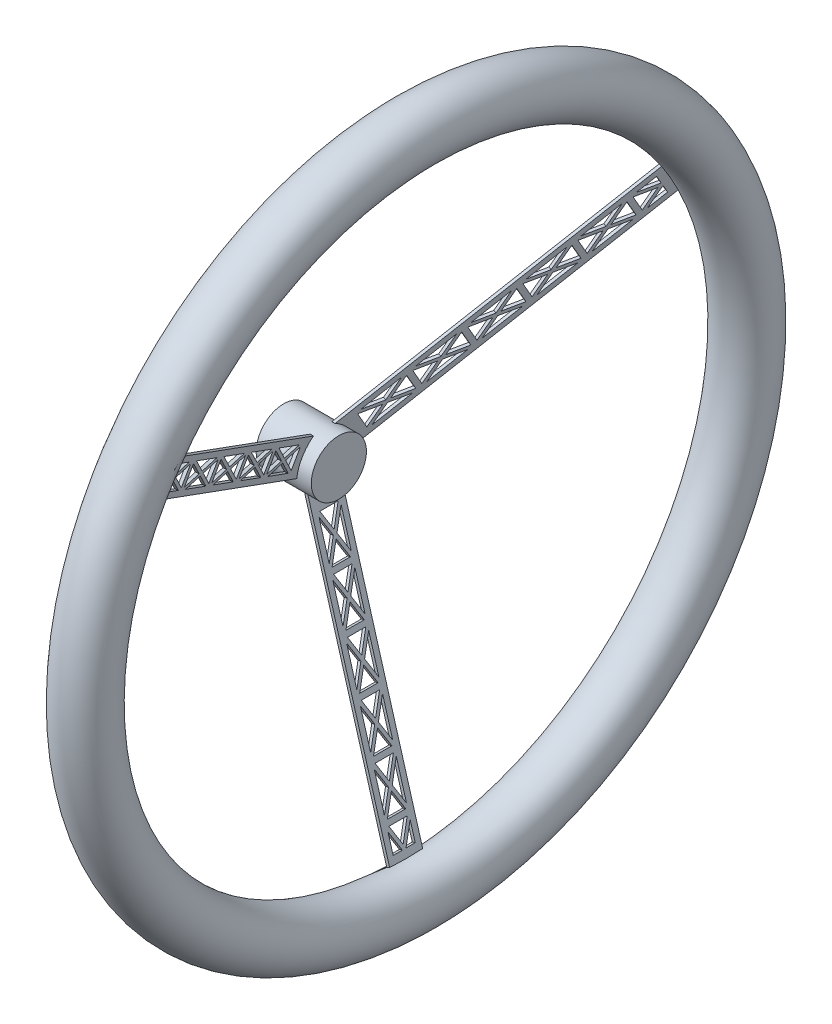
SolidWorks part; units mm, degrees
material "AISI 1035 Çelik (SS)"
ref_plane "Ön Düzlem" through (0, 0, 0) normal (0, 0, 1) x (1, 0, 0)
ref_plane "Üst Düzlem" through (0, 0, 0) normal (0, 1, 0) x (1, 0, 0)
ref_plane "Sağ Düzlem" through (0, 0, 0) normal (1, 0, 0) x (0, 0, -1)
sketch "Çizim3" plane through (0, 0, 0) normal (0, 0, 1) x (1, 0, 0)
  line L0 (0, 0) -> (0, 150) construction
  line L1 (0, 0) -> (50, 0) construction
  circle A0 centre (0, 150) radius 12.5
  dimension "D2" = 25
  dimension "D1" = 150
revolve "Döndür1" add sketch "Çizim3" angle 360 about L1
sketch "Çizim5" plane through (0, 0, 0) normal (1, 0, 0) x (0, 0, -1)
  circle A0 centre (0, 0) radius 7.5
  circle A1 centre (0, 0) radius 12.5
  dimension "D1" = 15
  dimension "D2" = 25
extrude "Yükseklik-Ekstrüzyon1" add sketch "Çizim5" against normal blind 20 from offset 40 separate body offset against normal yes
extrude "Yükseklik-Ekstrüzyon2" add sketch "Çizim5<2>" along normal blind 5 from offset 40 contours A0 | A1 A0 region at (0, 0, 0) region at (0, 0, 12.1464) offset against normal yes
sketch "Çizim5<2>" plane through (0, 0, 0) normal (1, 0, 0) x (0, 0, -1) same geometry as "Çizim5"
sketch "Çizim6" plane through (0, 0, 0) normal (0, 0, 1) x (1, 0, 0)
  line L0 (1.3337, -158.2302) -> (-42.6246, -6.5159)
  line L1 (-0.1663, -158.0735) -> (-44.0792, -6.5159)
  line L2 (-0.1663, -158.0735) -> (1.3337, -158.2302)
  line L3 (-44.0792, -6.5159) -> (-42.6246, -6.5159)
  dimension "D1" = 1.5
extrude "Yükseklik-Ekstrüzyon3" add sketch "Çizim6" along normal mid plane 15 contours L1 L3 L0 L2
sketch "Çizim7" plane through (-41.0651, -11.8984, 0) normal (0.9605, 0.2783, 0) x (0, 0, -1)
  line L0 (-7.5, -5.7205) -> (-7.5, -124.8484) construction
  line L1 (-7.5, -131.4244) -> (-7.5, 1.9764) construction
  line L2 (-7.5, -5.7205) -> (-5, -5.7205) construction
  line L3 (7.5, -131.4244) -> (7.5, 1.9764) construction
  line L4 (7.5, -5.7205) -> (7.5, -124.8484) construction
  line L5 (-5, -7.3976) -> (-0.8385, -15.7205)
  line L6 (-4.1615, -25.7205) -> (-5, -25.7205) construction
  line L7 (-4.1615, -5.7205) -> (0, -14.0435)
  line L8 (-4.1615, -5.7205) -> (4.1615, -5.7205)
  line L9 (-5, -7.3976) -> (-5, -24.0435)
  line L10 (-4.1615, -25.7205) -> (4.1615, -25.7205)
  line L11 (5, -7.3976) -> (5, -24.0435)
  line L12 (0, -14.0435) -> (4.1615, -5.7205)
  line L13 (0, -17.3976) -> (4.1615, -25.7205)
  line L15 (-4.1615, -25.7205) -> (0, -17.3976)
  line L16 (-5, -24.0435) -> (-0.8385, -15.7205)
  line L18 (0.8385, -15.7205) -> (5, -7.3976)
  line L19 (0.8385, -15.7205) -> (5, -24.0435)
  line L20 (5, -5.7205) -> (7.5, -5.7205) construction
  line L21 (-4.1615, -5.7205) -> (4.1615, -5.7205) construction
  line L22 (-5, -25.7205) -> (-5, -24.0435) construction
  line L24 (-5, -7.3976) -> (-5, -5.7205) construction
  line L25 (-5, -5.7205) -> (-4.1615, -5.7205) construction
  line L26 (-5, -25.7205) -> (-5, -28.2205) construction
  line L28 (-5, -29.8976) -> (-0.8385, -38.2205)
  line L29 (-4.1615, -48.2205) -> (-5, -48.2205) construction
  line L30 (-4.1615, -28.2205) -> (0, -36.5435)
  line L31 (-4.1615, -28.2205) -> (4.1615, -28.2205)
  line L32 (-5, -29.8976) -> (-5, -46.5435)
  line L33 (-4.1615, -48.2205) -> (4.1615, -48.2205)
  line L34 (5, -29.8976) -> (5, -46.5435)
  line L35 (0, -36.5435) -> (4.1615, -28.2205)
  line L36 (0, -39.8976) -> (4.1615, -48.2205)
  line L37 (-4.1615, -48.2205) -> (0, -39.8976)
  line L38 (-5, -46.5435) -> (-0.8385, -38.2205)
  line L39 (0.8385, -38.2205) -> (5, -29.8976)
  line L40 (0.8385, -38.2205) -> (5, -46.5435)
  line L41 (-5, -48.2205) -> (-5, -46.5435) construction
  line L42 (-5, -29.8976) -> (-5, -28.2205) construction
  line L43 (-5, -28.2205) -> (-4.1615, -28.2205) construction
  line L44 (-5, -48.2205) -> (-5, -50.7205) construction
  line L45 (-5, -52.3976) -> (-0.8385, -60.7205)
  line L46 (-4.1615, -70.7205) -> (-5, -70.7205) construction
  line L47 (-4.1615, -50.7205) -> (0, -59.0435)
  line L48 (-4.1615, -50.7205) -> (4.1615, -50.7205)
  line L49 (-5, -52.3976) -> (-5, -69.0435)
  line L50 (-4.1615, -70.7205) -> (4.1615, -70.7205)
  line L51 (5, -52.3976) -> (5, -69.0435)
  line L52 (0, -59.0435) -> (4.1615, -50.7205)
  line L53 (0, -62.3976) -> (4.1615, -70.7205)
  line L54 (-4.1615, -70.7205) -> (0, -62.3976)
  line L55 (-5, -69.0435) -> (-0.8385, -60.7205)
  line L56 (0.8385, -60.7205) -> (5, -52.3976)
  line L57 (0.8385, -60.7205) -> (5, -69.0435)
  line L58 (-5, -70.7205) -> (-5, -69.0435) construction
  line L59 (-5, -52.3976) -> (-5, -50.7205) construction
  line L60 (-5, -50.7205) -> (-4.1615, -50.7205) construction
  line L61 (-5, -70.7205) -> (-5, -73.2205) construction
  line L62 (-5, -74.8976) -> (-0.8385, -83.2205)
  line L63 (-4.1615, -93.2205) -> (-5, -93.2205) construction
  line L64 (-4.1615, -73.2205) -> (0, -81.5435)
  line L65 (-4.1615, -73.2205) -> (4.1615, -73.2205)
  line L66 (-5, -74.8976) -> (-5, -91.5435)
  line L67 (-4.1615, -93.2205) -> (4.1615, -93.2205)
  line L68 (5, -74.8976) -> (5, -91.5435)
  line L69 (0, -81.5435) -> (4.1615, -73.2205)
  line L70 (0, -84.8976) -> (4.1615, -93.2205)
  line L71 (-4.1615, -93.2205) -> (0, -84.8976)
  line L72 (-5, -91.5435) -> (-0.8385, -83.2205)
  line L73 (0.8385, -83.2205) -> (5, -74.8976)
  line L74 (0.8385, -83.2205) -> (5, -91.5435)
  line L75 (-5, -93.2205) -> (-5, -91.5435) construction
  line L76 (-5, -74.8976) -> (-5, -73.2205) construction
  line L77 (-5, -73.2205) -> (-4.1615, -73.2205) construction
  line L78 (-5, -93.2205) -> (-5, -95.7205) construction
  line L79 (-5, -97.3976) -> (-0.8385, -105.7205)
  line L80 (-4.1615, -115.7205) -> (-5, -115.7205) construction
  line L81 (-4.1615, -95.7205) -> (0, -104.0435)
  line L82 (-4.1615, -95.7205) -> (4.1615, -95.7205)
  line L83 (-5, -97.3976) -> (-5, -114.0435)
  line L84 (-4.1615, -115.7205) -> (4.1615, -115.7205)
  line L85 (5, -97.3976) -> (5, -114.0435)
  line L86 (0, -104.0435) -> (4.1615, -95.7205)
  line L87 (0, -107.3976) -> (4.1615, -115.7205)
  line L88 (-4.1615, -115.7205) -> (0, -107.3976)
  line L89 (-5, -114.0435) -> (-0.8385, -105.7205)
  line L90 (0.8385, -105.7205) -> (5, -97.3976)
  line L91 (0.8385, -105.7205) -> (5, -114.0435)
  line L92 (-5, -115.7205) -> (-5, -114.0435) construction
  line L93 (-5, -97.3976) -> (-5, -95.7205) construction
  line L94 (-5, -95.7205) -> (-4.1615, -95.7205) construction
  line L95 (-5, -115.7205) -> (-5, -118.2205) construction
  line L96 (-5, -119.8976) -> (-0.8385, -128.2205)
  line L97 (-0.8385, -128.2205) -> (-5, -128.2205)
  line L98 (-4.1615, -118.2205) -> (0, -126.5435)
  line L99 (-4.1615, -118.2205) -> (4.1615, -118.2205)
  line L100 (-5, -119.8976) -> (-5, -128.2205)
  line L102 (5, -119.8976) -> (5, -128.2205)
  line L103 (0, -126.5435) -> (4.1615, -118.2205)
  line L107 (0.8385, -128.2205) -> (5, -119.8976)
  line L110 (-5, -119.8976) -> (-5, -118.2205) construction
  line L111 (-5, -118.2205) -> (-4.1615, -118.2205) construction
  line L112 (5, -128.2205) -> (0.8385, -128.2205)
  dimension "D1" = 2.5
  dimension "D2" = 2.5
  dimension "D3" = 10
  dimension "D4" = 2.5
  dimension "D5" = 2.5
  dimension "D6" = 2.5
extrude "Kes-Ekstrüzyon3" cut sketch "Çizim7" against normal blind 1.5
pattern_circular "Dairesel Kaplama1" count 3 every 120 about axis through (-35, 0, 0) along (1, 0, 0) of "Yükseklik-Ekstrüzyon3"
pattern_circular "Dairesel Kaplama2" count 3 every 120 about axis through (-35, 0, 0) along (1, 0, 0) of "Kes-Ekstrüzyon3"
